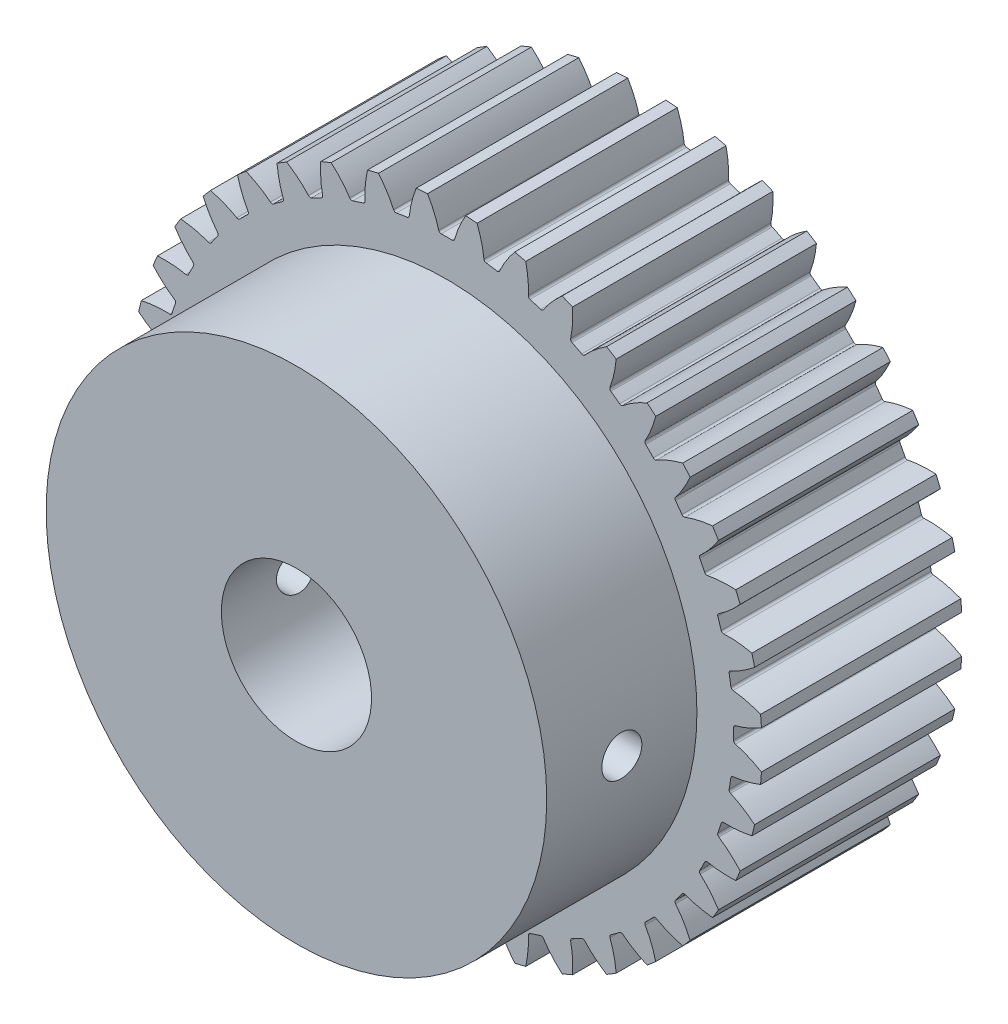
SolidWorks part; units mm, degrees
ref_plane "Front Plane" through (0, 0, 0) normal (0, 0, 1) x (1, 0, 0)
ref_plane "Top Plane" through (0, 0, 0) normal (0, 1, 0) x (1, 0, 0)
ref_plane "Right Plane" through (0, 0, 0) normal (1, 0, 0) x (0, 0, -1)
sketch "Sketch1" plane through (0, 0, 0) normal (0, 0, 1) x (1, 0, 0)
  line L0 (0, 30) -> (0, -30) construction
  line L1 (0, -30) -> (8.8305, -30) construction
  line L2 (0, -30) -> (9.6418, -26.4907) construction
  line L3 (0, 0) -> (9.6418, -26.4907)
  line L4 (0, 0) -> (-28.1284, 0) construction
  line L5 (-28.1284, 1.875) -> (-28.1284, -1.875) construction
  line L6 (-28.1284, 1.875) -> (0, 0) construction
  line L7 (0, 0) -> (-28.1284, -1.875) construction
  line L8 (0, 0) -> (-20.6686, 19.1711) construction
  line L9 (0, 0) -> (-17.9401, 21.7456) construction
  line L10 (0, 0) -> (-14.894, 23.9351) construction
  line L11 (0, 0) -> (-11.5842, 25.7007) construction
  line L12 (0, 0) -> (-8.0692, 27.0113) construction
  line L13 (0, 0) -> (-4.4113, 27.8435) construction
  line L14 (-4.4113, 27.8435) -> (-0.7075, 28.4303) construction
  line L15 (-8.0692, 27.0113) -> (-0.883, 29.158) construction
  line L16 (-11.5842, 25.7007) -> (-1.3279, 30.3236) construction
  line L17 (-14.894, 23.9351) -> (-2.1584, 31.86) construction
  line L18 (-17.9401, 21.7456) -> (-3.4769, 33.6778) construction
  line L19 (-20.6686, 19.1711) -> (-5.3675, 35.6673) construction
  circle A0 centre (0, 0) radius 28.1908 construction
  arc A1 (1.1779, 29.9769) -> (-1.1779, 29.9769) centre (0, 0) ccw construction
  circle A2 centre (0, 30) radius 1.1781 construction
  circle A3 centre (0, 0) radius 28.6595
  circle A4 centre (0, 0) radius 31.5
  circle A5 centre (0, 0) radius 7.5
  circle A6 centre (0, 0) radius 25
  spline S0 degree 3 poles (-5.3675, 35.6673) (-4.1503, 34.5369) (-2.6529, 32.8286) (-1.3674, 30.4884) (-0.9147, 29.3232) (-0.6834, 28.4341) (-0.6286, 27.5171) (-0.6989, 26.269) (-1.1981, 23.646) (-2.0942, 21.5586) (-2.9023, 20.1072) knots 0 0 0 0 0.285711 0.385711 0.45714 0.5 0.54286 0.614289 0.714289 1 1 1 1
  spline S1 degree 3 poles (5.3675, 35.6673) (4.1503, 34.5369) (2.6529, 32.8286) (1.3674, 30.4884) (0.9147, 29.3232) (0.6834, 28.4341) (0.6286, 27.5171) (0.6989, 26.269) (1.1981, 23.646) (2.0942, 21.5586) (2.9023, 20.1072) knots 0 0 0 0 0.285711 0.385711 0.45714 0.5 0.54286 0.614289 0.714289 1 1 1 1
  point P3 (-2.9023, 20.1072)
  point P4 (0, 0)
  point P16 (-28.1284, 0)
  point P27 (-1.7192, 22.5838)
  point P28 (-1.0272, 24.72)
  point P29 (-0.7123, 26.438)
  point P30 (-0.6494, 27.684)
  dimension "D4" = 2.3562
  dimension "D17" = 63
  dimension "D18" = 57.3191
  dimension "D19" = 15
  dimension "D20" = 50
  dimension "D1" = 20
  dimension "D2" = 60
  dimension "D3" = 90
  dimension "D5" = 3.75
  dimension "D6" = 7.63
  dimension "D7" = 7.63
  dimension "D8" = 7.63
  dimension "D9" = 7.63
  dimension "D10" = 7.63
  dimension "D11" = 3.75
  dimension "D12" = 7.5
  dimension "D13" = 11.25
  dimension "D14" = 15
  dimension "D15" = 18.75
  dimension "D16" = 22.5
extrude "Boss-Extrude1" add sketch "Sketch1" along normal blind 20 contours A4
extrude "Cut-Extrude2" cut sketch "Sketch1<5>" along normal through all contours S1 A4 S0 A3 region at (0, 30.2907, 0)
sketch "Sketch1<5>" plane through (0, 0, 0) normal (0, 0, 1) x (1, 0, 0) same geometry as "Sketch1"
fillet "Fillet1" radius 0.25 2 edges at (0.7485, 28.6498, 10) (-0.7485, 28.6498, 10)
pattern_circular "CirPattern1" count 40 over 360 about axis through (0, 0, 20) along (0, 0, -1) of "Cut-Extrude2", "Fillet1" reverse direction yes
extrude "Boss-Extrude2" add sketch "Sketch1<8>" along normal blind 35 contours A6
sketch "Sketch1<8>" plane through (0, 0, 0) normal (0, 0, 1) x (1, 0, 0) same geometry as "Sketch1"
sketch "Sketch2" plane through (0, 0, 0) normal (0, 0, -1) x (-1, 0, 0)
  circle A0 centre (0, 0) radius 7.5
  dimension "D1" = 15
extrude "Cut-Extrude4" cut sketch "Sketch2" against normal through all
ref_plane "Plane1" through (25, 0, 0) normal (1, 0, 0) x (0, 0, -1)
sketch "Sketch3" plane through (25, 0, 0) normal (1, 0, 0) x (0, 0, -1)
  line L0 (-35, 0) -> (0, 0) construction
  line L1 (-35, 25) -> (-35, -25) construction
  line L2 (-35, 0) -> (-27.5, 0) construction
  circle A0 centre (-27.5, 0) radius 2
  dimension "D1" = 7.5
extrude "Cut-Extrude6" cut sketch "Sketch3" against normal through all contours A0
equation "\"boss\"= 50mm"
equation "\"bore\"= 15mm"
equation "\"pcd\"= 60mm"
equation "\"d\"= 63mm"
equation "\"e\"= 7.63"
equation "\"x\"= 3.75"
equation "\"y\"= 1"
equation "\"z\"= 1"
equation "\"D2@Sketch1\"=\"pcd\""
equation "\"D4@Sketch1\"=3/4*pi"
equation "\"D6@Sketch1\"=\"e\""
equation "\"D7@Sketch1\"=\"e\""
equation "\"D8@Sketch1\"=\"e\""
equation "\"D9@Sketch1\"=\"e\""
equation "\"D10@Sketch1\"=\"e\""
equation "\"D12@Sketch1\"=\"x\"*2"
equation "\"D13@Sketch1\"=\"x\"*3"
equation "\"D14@Sketch1\"=\"x\"*4"
equation "\"D15@Sketch1\"=\"x\"*5"
equation "\"D16@Sketch1\"=\"x\"*6"
equation "\"D17@Sketch1\"=\"d\""
equation "\"D19@Sketch1\"=\"bore\""
equation "\"D20@Sketch1\"=\"boss\""
equation "\"D1@Sketch2\"=\"bore\""
